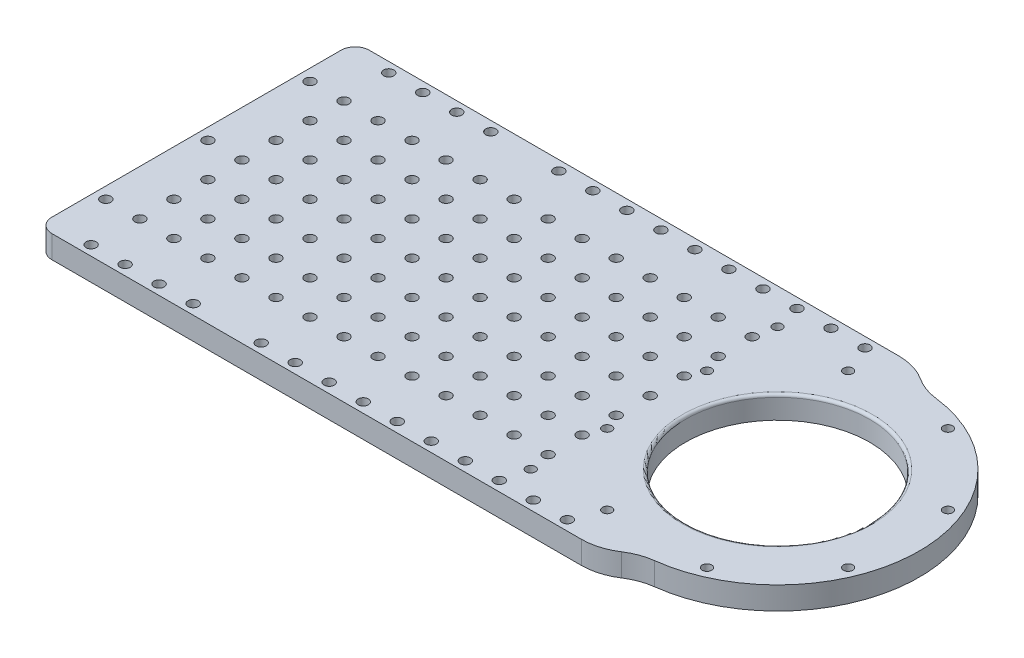
SolidWorks part; units mm, degrees
material "6061 Alloy"
ref_plane "Front Plane" through (0, 0, 0) normal (0, 0, 1) x (1, 0, 0)
ref_plane "Top Plane" through (0, 0, 0) normal (0, 1, 0) x (1, 0, 0)
ref_plane "Right Plane" through (0, 0, 0) normal (1, 0, 0) x (0, 0, -1)
sketch "Sketch1" plane through (0, 0, 0) normal (0, 1, 0) x (1, 0, 0)
  line L1 (-100, 56) -> (100, 56)
  line L2 (-100, 56) -> (-100, -56)
  line L3 (-100, -56) -> (100, -56)
  line L4 (100, 56) -> (100, -56)
  line L5 (-100, 56) -> (100, -56) construction
  line L6 (-100, -56) -> (100, 56) construction
  point P0 (0, 0)
  dimension "D1" = 200
  dimension "D2" = 112
extrude "Boss-Extrude1" add sketch "Sketch1" along normal blind 8
sketch "Sketch3" plane through (0, 0, 0) normal (0, 1, 0) x (1, 0, 0)
  line L0 (-100, 0) -> (-110, 0)
  line L1 (-100, 56) -> (-100, -56) construction
  line L2 (-110, 25) -> (-110, -25)
  line L3 (-110, 25) -> (-100, 56)
  line L4 (-110, -25) -> (-100, -56)
  line L5 (-100, -56) -> (-100, 56)
  point P8 (-110, 0)
  dimension "D1" = 50
extrude "Boss-Extrude2" add sketch "Sketch3" along normal blind 8 contours L0 L5 L3 L2 | L4 L5 L0 L2 region at (-104.3621, 0, 21.2387) region at (-104.3621, 0, -21.2387)
fillet "Fillet1" radius 10 4 edges at (-100, 4, 56) (-110, 4, 25) (-110, 4, -25) (-100, 4, -56)
sketch "Sketch5" plane through (0, 0, 0) normal (0, 1, 0) x (1, 0, 0)
  line L1 (100, 56) -> (157.9995, 56)
  line L2 (100, 56) -> (100, -56)
  line L3 (100, -56) -> (157.9995, -56)
  line L4 (157.9995, 56) -> (157.9995, -56)
  dimension "D1" = 112
extrude "Boss-Extrude3" add sketch "Sketch5" along normal blind 8
sketch "Sketch8" plane through (0, 8, 0) normal (0, 1, 0) x (1, 0, 0)
  line L0 (106.9378, 56) -> (106.9378, -56)
  line L1 (157.9995, 56) -> (-92.7184, 56) construction
  line L2 (-92.7184, -56) -> (157.9995, -56) construction
  line L3 (106.9378, 0) -> (156.9378, 0)
  line L4 (106.9378, -56) -> (131.9378, -56)
  line L5 (131.9378, -56) -> (156.9378, -50)
  line L6 (131.9378, 56) -> (156.9378, 50)
  line L7 (106.9378, 56) -> (131.9378, 56)
  circle A0 centre (156.9378, 0) radius 50
  line M16 (157.9995, -56) -> (157.9995, 56)
  dimension "D1" = 25
extrude "Boss-Extrude4" add sketch "Sketch8" against normal blind 8 contours A0 M16 region at (178.7334, 8, 0)
fillet "Fillet2" radius 20 2 edges at (157.9995, 4, 56) (157.9995, 4, -56)
fillet "Fillet3" radius 20 2 edges at (157.9995, 4, 49.9887) (157.9995, 4, -49.9887)
sketch "Sketch10" plane through (0, 8, 0) normal (0, 1, 0) x (1, 0, 0)
  line L0 (110.9378, 0) -> (202.9378, 0)
  line L1 (114.4408, 17.6069) -> (114.4379, -17.6)
  line L2 (-92.7184, -56) -> (143.7056, -56) construction
  circle A0 centre (156.9378, 0) radius 46
  circle A3 centre (114.4408, 17.6069) radius 1.65
  circle A4 centre (139.3378, 42.4999) radius 1.65
  circle A5 centre (174.5447, 42.497) radius 1.65
  circle A6 centre (199.4377, 17.6) radius 1.65
  circle A7 centre (199.4349, -17.6069) radius 1.65
  circle A8 centre (174.5378, -42.4999) radius 1.65
  circle A9 centre (139.331, -42.497) radius 1.65
  circle A10 centre (114.4379, -17.6) radius 1.65
  dimension "D1" = 8
  dimension "D5" = 3.3
  dimension "D3" = 92
  dimension "D4" = 17.6
  dimension "D2" = 35.2069
  dimension "D6" = 56
extrude "Cut-Extrude4" cut sketch "Sketch10" against normal blind 10 contours A10 | A3 | A4 | A5 | A9 | A8 | A7 | A6
sketch "Sketch11" plane through (0, 8, 0) normal (0, 1, 0) x (1, 0, 0)
  line L2 (139.331, -42.497) -> (139.289, -42.7462)
  line L4 (174.5378, -42.4999) -> (199.4349, -17.6069)
  line L8 (139.3378, 42.4999) -> (114.4408, 17.6069)
  line L9 (156.9378, 50) -> (106.9378, 50)
  line L10 (106.9378, 50) -> (106.9378, 0)
  line L11 (106.9378, 0) -> (106.9378, -50)
  line L12 (106.9378, -50) -> (156.9378, -50)
  line L13 (106.9378, 50) -> (113.4008, 43.537)
  line L14 (106.9378, 0) -> (113.4008, 0)
  circle A1 centre (113.4008, 43.537) radius 1.65
  circle A2 centre (113.4008, -43.537) radius 1.65
extrude "Cut-Extrude5" cut sketch "Sketch11" against normal blind 10 contours A1 | A2 region at (112.7872, 8, -42.0558) region at (113.4008, 8, 43.537)
sketch "Sketch13" plane through (0, 8, 0) normal (0, 1, 0) x (1, 0, 0)
  line L0 (-106.5, 0) -> (-84.1762, 0)
  line L5 (-98.9045, 47.9955) -> (-106.1861, 25.4225)
  line L7 (-98.9045, 47.9955) -> (-106.1861, 25.4225)
  line L10 (-92.7184, -52.5) -> (143.7056, -52.5)
  line L11 (143.7056, 52.5) -> (-92.7184, 52.5)
  line L13 (-106.5, 23.427) -> (-106.5, -23.427)
  line L14 (-106.5, 23.427) -> (-106.5, -23.427)
  line L15 (-92.7184, -52.5) -> (143.7056, -52.5)
  line L16 (143.7056, 52.5) -> (-92.7184, 52.5)
  line L20 (-106.1861, -25.4225) -> (-98.9045, -47.9955)
  line L21 (-106.1861, -25.4225) -> (-98.9045, -47.9955)
  circle A0 centre (-92.7184, -52.5) radius 1.8
  circle A1 centre (-80.7184, -52.5) radius 1.8
  circle A2 centre (-80.7184, 52.5) radius 1.8
  circle A3 centre (-68.7184, -52.5) radius 1.8
  circle A4 centre (-68.7184, 52.5) radius 1.8
  circle A5 centre (-56.7184, -52.5) radius 1.8
  circle A6 centre (-56.7184, 52.5) radius 1.8
  circle A7 centre (-44.7184, -52.5) radius 1.8
  circle A8 centre (-44.7184, 52.5) radius 1.8
  circle A9 centre (-92.7184, 52.5) radius 1.8
  circle A10 centre (-32.7184, -52.5) radius 1.8
  circle A11 centre (-32.7184, 52.5) radius 1.8
  circle A12 centre (-20.7184, -52.5) radius 1.8
  circle A13 centre (-20.7184, 52.5) radius 1.8
  circle A14 centre (-8.7184, -52.5) radius 1.8
  circle A15 centre (-8.7184, 52.5) radius 1.8
  circle A16 centre (3.2816, -52.5) radius 1.8
  circle A17 centre (3.2816, 52.5) radius 1.8
  circle A36 centre (15.2816, -52.5) radius 1.8
  circle A37 centre (15.2816, 52.5) radius 1.8
  circle A38 centre (27.2816, -52.5) radius 1.8
  circle A39 centre (27.2816, 52.5) radius 1.8
  circle A40 centre (39.2816, -52.5) radius 1.8
  circle A41 centre (39.2816, 52.5) radius 1.8
  circle A42 centre (51.2816, -52.5) radius 1.8
  circle A43 centre (51.2816, 52.5) radius 1.8
  circle A44 centre (63.2816, -52.5) radius 1.8
  circle A45 centre (63.2816, 52.5) radius 1.8
  circle A46 centre (75.2816, -52.5) radius 1.8
  circle A47 centre (75.2816, 52.5) radius 1.8
  circle A48 centre (87.2816, -52.5) radius 1.8
  circle A49 centre (87.2816, 52.5) radius 1.8
  circle A50 centre (99.2816, -52.5) radius 1.8
  circle A51 centre (99.2816, 52.5) radius 1.8
  circle A52 centre (111.2816, -52.5) radius 1.8
  circle A53 centre (111.2816, 52.5) radius 1.8
  circle A54 centre (123.2816, -52.5) radius 1.8
  circle A55 centre (123.2816, 52.5) radius 1.8
  circle A56 centre (135.2816, -52.5) radius 1.8
  circle A57 centre (135.2816, 52.5) radius 1.8
  arc A58 (143.7056, -52.5) -> (152.7479, -49.8017) centre (143.7056, -36) ccw
  arc A59 (143.7056, -52.5) -> (152.7479, -49.8017) centre (143.7056, -36) ccw
  arc A60 (162.7095, -46.1404) -> (152.7479, -49.8017) centre (165.6263, -69.4587) ccw
  arc A61 (162.7095, -46.1404) -> (152.7479, -49.8017) centre (165.6263, -69.4587) ccw
  arc A62 (162.7095, -46.1404) -> (162.7095, 46.1404) centre (156.9378, 0) ccw
  arc A63 (162.7095, -46.1404) -> (162.7095, 46.1404) centre (156.9378, 0) ccw
  arc A64 (152.7479, 49.8017) -> (162.7095, 46.1404) centre (165.6263, 69.4587) ccw
  arc A65 (152.7479, 49.8017) -> (162.7095, 46.1404) centre (165.6263, 69.4587) ccw
  arc A66 (152.7479, 49.8017) -> (143.7056, 52.5) centre (143.7056, 36) ccw
  arc A67 (152.7479, 49.8017) -> (143.7056, 52.5) centre (143.7056, 36) ccw
  arc A68 (-92.7184, 52.5) -> (-98.9045, 47.9955) centre (-92.7184, 46) ccw
  arc A69 (-92.7184, 52.5) -> (-98.9045, 47.9955) centre (-92.7184, 46) ccw
  arc A70 (-106.1861, 25.4225) -> (-106.5, 23.427) centre (-100, 23.427) ccw
  arc A71 (-106.1861, 25.4225) -> (-106.5, 23.427) centre (-100, 23.427) ccw
  arc A72 (-106.5, -23.427) -> (-106.1861, -25.4225) centre (-100, -23.427) ccw
  arc A73 (-106.5, -23.427) -> (-106.1861, -25.4225) centre (-100, -23.427) ccw
  arc A74 (-98.9045, -47.9955) -> (-92.7184, -52.5) centre (-92.7184, -46) ccw
  arc A75 (-98.9045, -47.9955) -> (-92.7184, -52.5) centre (-92.7184, -46) ccw
  dimension "D2" = 20
  dimension "D1" = 3.5
extrude "Cut-Extrude7" cut sketch "Sketch13" against normal blind 10 contours A9 | A2 | A4 | A6 | A13 | A15 | A17 | A39 | A41 | A43 | A45 | A47 | A49 | A51 | A53 | A55 | A57 | A56 | A54 | A52 | A50 | A48 | A46 | A40 | A38 | A16 | A14 | A12 | A5 | A0 | A1 | A3 | A44 | A42 | A10 | A11
sketch "Sketch14" plane through (0, 8, 0) normal (0, 1, 0) x (1, 0, 0)
  line L0 (-110, 0) -> (-70, 0)
  line L1 (-110, 23.427) -> (-110, -23.427) construction
  line L2 (-70, 0) -> (30, 0)
  circle A0 centre (-20, 0) radius 1.8
  circle A1 centre (-8, 0) radius 1.8
  circle A2 centre (4, 0) radius 1.8
  circle A3 centre (16, 0) radius 1.8
  circle A4 centre (28, 0) radius 1.8
  circle A5 centre (-32, 0) radius 1.8
  circle A6 centre (-44, 0) radius 1.8
  circle A7 centre (-56, 0) radius 1.8
  circle A8 centre (-68, 0) radius 1.8
  circle A9 centre (-68, 12) radius 1.8
  circle A17 centre (28, 12) radius 1.8
  circle A18 centre (-68, 24) radius 1.8
  circle A26 centre (28, 24) radius 1.8
  circle A27 centre (-68, 36) radius 1.8
  circle A28 centre (-56, 36) radius 1.8
  circle A29 centre (-44, 36) radius 1.8
  circle A30 centre (-32, 36) radius 1.8
  circle A31 centre (-20, 36) radius 1.8
  circle A32 centre (-8, 36) radius 1.8
  circle A33 centre (4, 36) radius 1.8
  circle A34 centre (16, 36) radius 1.8
  circle A35 centre (28, 36) radius 1.8
  circle A36 centre (-68, -12) radius 1.8
  circle A44 centre (28, -12) radius 1.8
  circle A45 centre (-68, -24) radius 1.8
  circle A53 centre (28, -24) radius 1.8
  circle A54 centre (-68, -36) radius 1.8
  circle A55 centre (-56, -36) radius 1.8
  circle A56 centre (-44, -36) radius 1.8
  circle A57 centre (-32, -36) radius 1.8
  circle A58 centre (-20, -36) radius 1.8
  circle A59 centre (-8, -36) radius 1.8
  circle A60 centre (4, -36) radius 1.8
  circle A61 centre (16, -36) radius 1.8
  circle A62 centre (28, -36) radius 1.8
  circle A63 centre (40, 36) radius 1.8
  circle A64 centre (40, 24) radius 1.8
  circle A65 centre (40, 12) radius 1.8
  circle A66 centre (40, 0) radius 1.8
  circle A69 centre (40, -36) radius 1.8
  circle A70 centre (52, 36) radius 1.8
  circle A73 centre (52, 0) radius 1.8
  circle A76 centre (52, -36) radius 1.8
  circle A77 centre (64, 36) radius 1.8
  circle A80 centre (64, 0) radius 1.8
  circle A83 centre (64, -36) radius 1.8
  circle A84 centre (76, 36) radius 1.8
  circle A87 centre (76, 0) radius 1.8
  circle A90 centre (76, -36) radius 1.8
  circle A91 centre (88, 36) radius 1.8
  circle A94 centre (88, 0) radius 1.8
  circle A97 centre (88, -36) radius 1.8
  circle A98 centre (100, 36) radius 1.8
  circle A101 centre (100, 0) radius 1.8
  circle A104 centre (100, -36) radius 1.8
  circle A105 centre (112, 36) radius 1.8
  circle A106 centre (112, 24) radius 1.8
  circle A107 centre (112, 12) radius 1.8
  circle A108 centre (112, 0) radius 1.8
  circle A109 centre (112, -12) radius 1.8
  circle A110 centre (112, -24) radius 1.8
  circle A111 centre (112, -36) radius 1.8
  circle A112 centre (-56, -12) radius 1.8 [skipped]
  circle A113 centre (-44, -12) radius 1.8 [skipped]
  circle A114 centre (-32, -12) radius 1.8 [skipped]
  circle A115 centre (-20, -12) radius 1.8 [skipped]
  circle A116 centre (-8, -12) radius 1.8 [skipped]
  circle A117 centre (4, -12) radius 1.8 [skipped]
  circle A118 centre (16, -12) radius 1.8 [skipped]
  circle A119 centre (-56, -24) radius 1.8 [skipped]
  circle A120 centre (-44, -24) radius 1.8 [skipped]
  circle A121 centre (-32, -24) radius 1.8 [skipped]
  circle A122 centre (-20, -24) radius 1.8 [skipped]
  circle A123 centre (-8, -24) radius 1.8 [skipped]
  circle A124 centre (4, -24) radius 1.8 [skipped]
  circle A125 centre (16, -24) radius 1.8 [skipped]
  circle A126 centre (-56, 12) radius 1.8 [skipped]
  circle A127 centre (-44, 12) radius 1.8 [skipped]
  circle A128 centre (-32, 12) radius 1.8 [skipped]
  circle A129 centre (-20, 12) radius 1.8 [skipped]
  circle A130 centre (-8, 12) radius 1.8 [skipped]
  circle A131 centre (4, 12) radius 1.8 [skipped]
  circle A132 centre (16, 12) radius 1.8 [skipped]
  circle A133 centre (-56, 24) radius 1.8 [skipped]
  circle A134 centre (-44, 24) radius 1.8 [skipped]
  circle A135 centre (-32, 24) radius 1.8 [skipped]
  circle A136 centre (-20, 24) radius 1.8 [skipped]
  circle A137 centre (-8, 24) radius 1.8 [skipped]
  circle A138 centre (4, 24) radius 1.8 [skipped]
  circle A139 centre (16, 24) radius 1.8 [skipped]
  circle A140 centre (52, 24) radius 1.8 [skipped]
  circle A141 centre (52, 12) radius 1.8 [skipped]
  circle A142 centre (64, 24) radius 1.8 [skipped]
  circle A143 centre (64, 12) radius 1.8 [skipped]
  circle A144 centre (76, 24) radius 1.8 [skipped]
  circle A145 centre (76, 12) radius 1.8 [skipped]
  circle A146 centre (88, 24) radius 1.8 [skipped]
  circle A147 centre (88, 12) radius 1.8 [skipped]
  circle A148 centre (100, 24) radius 1.8 [skipped]
  circle A149 centre (100, 12) radius 1.8 [skipped]
  circle A150 centre (40, -12) radius 1.8 [skipped]
  circle A151 centre (40, -24) radius 1.8 [skipped]
  circle A152 centre (52, -12) radius 1.8 [skipped]
  circle A153 centre (52, -24) radius 1.8 [skipped]
  circle A154 centre (64, -12) radius 1.8 [skipped]
  circle A155 centre (64, -24) radius 1.8 [skipped]
  circle A156 centre (76, -12) radius 1.8 [skipped]
  circle A157 centre (76, -24) radius 1.8 [skipped]
  circle A158 centre (88, -12) radius 1.8 [skipped]
  circle A159 centre (88, -24) radius 1.8 [skipped]
  circle A160 centre (100, -12) radius 1.8 [skipped]
  circle A161 centre (100, -24) radius 1.8 [skipped]
  circle A162 centre (40, -12) radius 1.8
  circle A163 centre (40, -24) radius 1.8
  dimension "D1" = 5
  dimension "D2" = 5
  dimension "D3" = 4
  dimension "D4" = 4
  dimension "D5" = 8
  dimension "D6" = 3
extrude "Cut-Extrude12" cut sketch "Sketch14" against normal blind 10 contours L2 A0 | L2 A0 | A73 | A80 | A63 | A70 | A27 | A18 | A28 | A29 | A30 | A31 | A32 | A33 | A34 | A9 | A8 | A7 | A36 | A45 | A54 | A55 | A56 | A57 | A58 | A59 | A60 | A61 | A62 | A53 | A44 | A4 | A3 | A2 | A1 | A5 | A6 | A17 | A26 | A64 | A65 | A66 | A162 | A35 | A77 | A84 | A91 | A98 | A105 | A106 | A111 | A104 | A97 | A90 | A83 | A76 | A69 | A163 | A87 | A94 | A101 | A108 | A109 | A110 | A107 region at (-20, 8, -0.7639) region at (-20, 8, 0.7639) region at (40, 8, -36) region at (52, 8, -36) region at (52, 8, 0) region at (64, 8, 0)
sketch "Sketch15" plane through (0, 8, 0) normal (0, 1, 0) x (1, 0, 0)
  line L0 (206.9378, 0) -> (-48.0622, 0)
  line L2 (-48.0622, 62.6241) -> (-123.4657, 62.6241)
  line L3 (-48.0622, 62.6241) -> (-48.0622, -83.2305)
  line L4 (-48.0622, -83.2305) -> (-123.4657, -83.2305)
  line L5 (-123.4657, 62.6241) -> (-123.4657, -83.2305)
  arc A0 (163.1439, -49.6134) -> (163.1439, 49.6134) centre (156.9378, 0) ccw construction
  dimension "D1" = 255
extrude "Cut-Extrude13" cut sketch "Sketch15" against normal blind 10 contours L3 L2 L5 L4
fillet "Fillet4" radius 5 2 edges at (-48.0622, 4, -56) (-48.0622, 4, 56)
sketch "Sketch16" plane through (0, 8, 0) normal (0, 1, 0) x (1, 0, 0)
  circle A0 centre (156.9378, 0) radius 32.5
  dimension "D1" = 65
extrude "Cut-Extrude16" cut sketch "Sketch16" against normal blind 10
fillet "Fillet8" radius 1 1 edges at (156.9378, 8, 32.5)
sketch "Sketch17" plane through (0, 8, 0) normal (0, 1, 0) x (1, 0, 0)
  circle A0 centre (-32, 36) radius 1.8
  circle A1 centre (-20, 36) radius 1.8
  circle A2 centre (-8, 36) radius 1.8
  circle A3 centre (4, 36) radius 1.8
  circle A4 centre (16, 36) radius 1.8
  circle A5 centre (28, 36) radius 1.8
  circle A6 centre (40, 36) radius 1.8
  circle A7 centre (52, 36) radius 1.8
  circle A8 centre (64, 36) radius 1.8
  circle A9 centre (76, 36) radius 1.8
  circle A10 centre (88, 36) radius 1.8
  circle A11 centre (100, 36) radius 1.8
  circle A12 centre (-20, 24) radius 1.8
  circle A13 centre (-8, 24) radius 1.8
  circle A14 centre (4, 24) radius 1.8
  circle A15 centre (16, 24) radius 1.8
  circle A16 centre (28, 24) radius 1.8
  circle A17 centre (40, 24) radius 1.8
  circle A18 centre (52, 24) radius 1.8
  circle A19 centre (64, 24) radius 1.8
  circle A20 centre (76, 24) radius 1.8
  circle A21 centre (88, 24) radius 1.8
  circle A22 centre (100, 24) radius 1.8
  circle A23 centre (-20, 12) radius 1.8
  circle A24 centre (-8, 12) radius 1.8
  circle A25 centre (4, 12) radius 1.8
  circle A26 centre (16, 12) radius 1.8
  circle A27 centre (28, 12) radius 1.8
  circle A28 centre (40, 12) radius 1.8
  circle A29 centre (52, 12) radius 1.8
  circle A30 centre (64, 12) radius 1.8
  circle A31 centre (76, 12) radius 1.8
  circle A32 centre (88, 12) radius 1.8
  circle A33 centre (100, 12) radius 1.8
  circle A34 centre (-20, 0) radius 1.8
  circle A35 centre (-8, 0) radius 1.8
  circle A36 centre (4, 0) radius 1.8
  circle A37 centre (16, 0) radius 1.8
  circle A38 centre (28, 0) radius 1.8
  circle A39 centre (40, 0) radius 1.8
  circle A40 centre (52, 0) radius 1.8
  circle A41 centre (64, 0) radius 1.8
  circle A42 centre (76, 0) radius 1.8
  circle A43 centre (88, 0) radius 1.8
  circle A44 centre (100, 0) radius 1.8
  circle A45 centre (-20, -12) radius 1.8
  circle A46 centre (-8, -12) radius 1.8
  circle A47 centre (4, -12) radius 1.8
  circle A48 centre (16, -12) radius 1.8
  circle A49 centre (28, -12) radius 1.8
  circle A50 centre (40, -12) radius 1.8
  circle A51 centre (52, -12) radius 1.8
  circle A52 centre (64, -12) radius 1.8
  circle A53 centre (76, -12) radius 1.8
  circle A54 centre (88, -12) radius 1.8
  circle A55 centre (100, -12) radius 1.8
  circle A56 centre (-20, -24) radius 1.8
  circle A57 centre (-8, -24) radius 1.8
  circle A58 centre (4, -24) radius 1.8
  circle A59 centre (16, -24) radius 1.8
  circle A60 centre (28, -24) radius 1.8
  circle A61 centre (40, -24) radius 1.8
  circle A62 centre (52, -24) radius 1.8
  circle A63 centre (64, -24) radius 1.8
  circle A64 centre (76, -24) radius 1.8
  circle A65 centre (88, -24) radius 1.8
  circle A66 centre (100, -24) radius 1.8
  circle A67 centre (-20, -36) radius 1.8
  circle A68 centre (-8, -36) radius 1.8
  circle A69 centre (4, -36) radius 1.8
  circle A70 centre (16, -36) radius 1.8
  circle A71 centre (28, -36) radius 1.8
  circle A72 centre (40, -36) radius 1.8
  circle A73 centre (52, -36) radius 1.8
  circle A74 centre (64, -36) radius 1.8
  circle A75 centre (76, -36) radius 1.8
  circle A76 centre (88, -36) radius 1.8
  circle A77 centre (100, -36) radius 1.8
  circle A78 centre (-32, 24) radius 1.8
  circle A79 centre (-32, 12) radius 1.8
  circle A80 centre (-32, 0) radius 1.8
  circle A81 centre (-32, -12) radius 1.8
  circle A82 centre (-32, -24) radius 1.8
  circle A83 centre (-32, -36) radius 1.8
  dimension "D1" = 12
  dimension "D2" = 7
extrude "Cut-Extrude17" cut sketch "Sketch17" against normal blind 10
